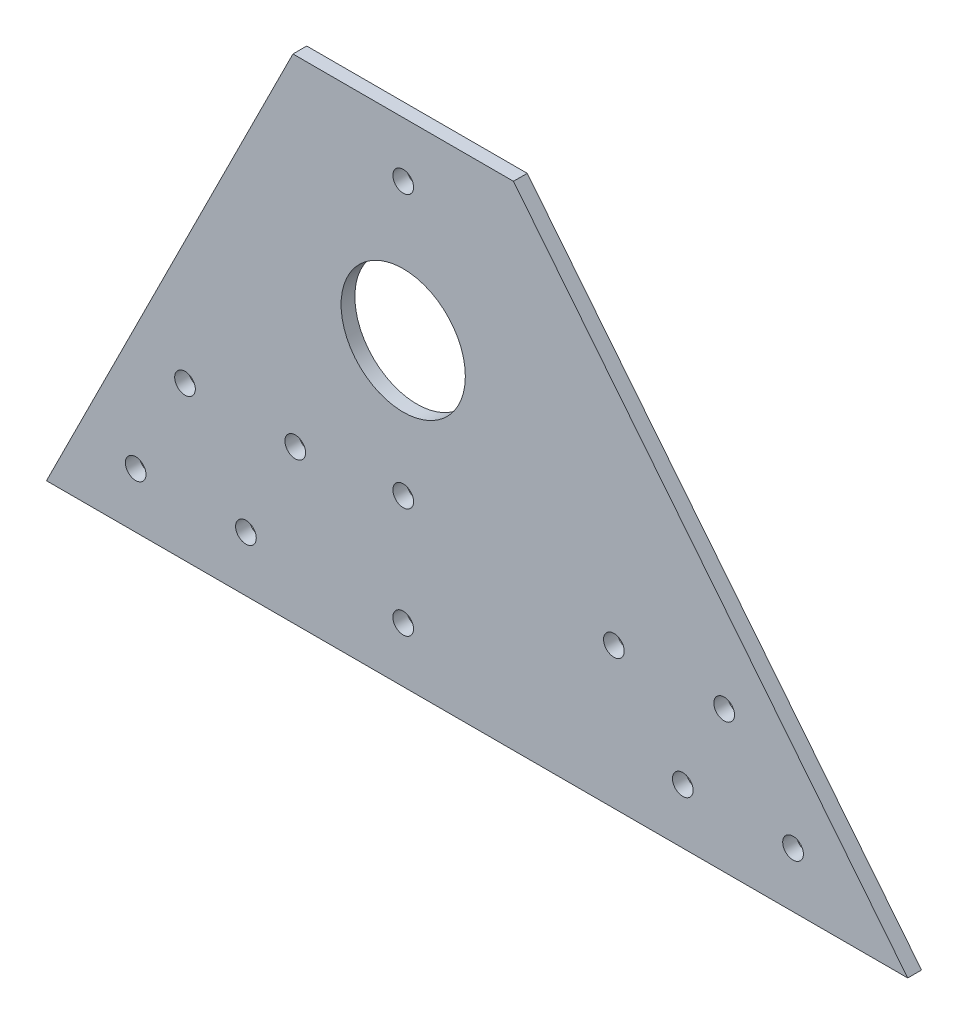
SolidWorks part; units mm, degrees
material "6063-T1"
ref_plane "Front Plane" through (0, 0, 0) normal (0, 0, 1) x (1, 0, 0)
ref_plane "Top Plane" through (0, 0, 0) normal (0, 1, 0) x (1, 0, 0)
ref_plane "Right Plane" through (0, 0, 0) normal (1, 0, 0) x (0, 0, -1)
sketch "Sketch1" plane through (0, 0, 0) normal (0, 0, 1) x (1, 0, 0)
  line L0 (25.4, 56.769) -> (116.231, -56.769)
  line L1 (-25.4, 56.769) -> (25.4, 56.769)
  line L2 (-25.4, 56.769) -> (-25.4, -56.769)
  line L3 (-25.4, -56.769) -> (25.4, -56.769)
  line L4 (25.4, 56.769) -> (25.4, -56.769)
  line L5 (-25.4, 56.769) -> (25.4, -56.769) construction
  line L6 (-25.4, -56.769) -> (25.4, 56.769) construction
  line L7 (116.231, -56.769) -> (25.4, -56.769)
  line L8 (-25.4, 56.769) -> (-82.1813, -56.769)
  line L9 (-82.1813, -56.769) -> (-25.4, -56.769)
  circle A0 centre (0, 12.319) radius 14.3129
  point P0 (0, 0)
  dimension "D3" = 28.6258
  dimension "D1" = 38.66
  dimension "D2" = 26.57
  dimension "D4" = 50.8
  dimension "D5" = 44.45
  dimension "D6" = 113.538
extrude "Boss-Extrude1" add sketch "Sketch1" along normal blind 3.175 contours L8 L9 L2 | L4 L1 L2 L3 A0 | L7 L0 L4 region at (24.1562, 0, 0) region at (55.677, -18.923, 0) region at (-44.3271, -18.923, 0)
sketch "Sketch2" plane through (0, 0, 3.175) normal (0, 0, 1) x (1, 0, 0)
  line L0 (-82.1813, -56.769) -> (116.231, -56.769) construction
  line L1 (-25.4, 56.769) -> (-82.1813, -56.769) construction
  line L2 (25.4, 56.769) -> (116.231, -56.769) construction
  circle A0 centre (-61.6302, -44.069) radius 2.3812
  circle A1 centre (-36.2302, -44.069) radius 2.3812
  circle A3 centre (-50.2691, -21.3515) radius 2.3813
  circle A4 centre (-24.8691, -21.3515) radius 2.3812
  circle A5 centre (64.407, -44.069) radius 2.3813
  circle A6 centre (89.807, -44.069) radius 2.3813
  circle A7 centre (48.5397, -24.235) radius 2.3813
  circle A8 centre (73.9397, -24.235) radius 2.3813
  dimension "D1" = 4.7625
  dimension "D2" = 4.7625
  dimension "D7" = 4.7625
  dimension "D8" = 4.7625
  dimension "D3" = 12.7
  dimension "D4" = 12.7
  dimension "D5" = 25.4
  dimension "D9" = 12.7
  dimension "D10" = 12.7
  dimension "D11" = 25.4
  dimension "D6" = 2
  dimension "D12" = 2
extrude "Cut-Extrude1" cut sketch "Sketch2" against normal through all
sketch "Sketch3" plane through (0, 0, 3.175) normal (0, 0, 1) x (1, 0, 0)
  line L0 (-25.4, 56.769) -> (25.4, 56.769) construction
  line L1 (-82.1813, -56.769) -> (116.231, -56.769) construction
  circle A0 centre (0, 44.069) radius 2.3812
  circle A1 centre (0, -18.669) radius 2.3813
  circle A2 centre (0, -44.069) radius 2.3812
  point P6 (0, 0)
  point P9 (0, 0)
  dimension "D1" = 4.7625
  dimension "D2" = 4.7625
  dimension "D3" = 4.7625
  dimension "D4" = 12.7
  dimension "D5" = 12.7
  dimension "D6" = 25.4
extrude "Cut-Extrude2" cut sketch "Sketch3" against normal through all
